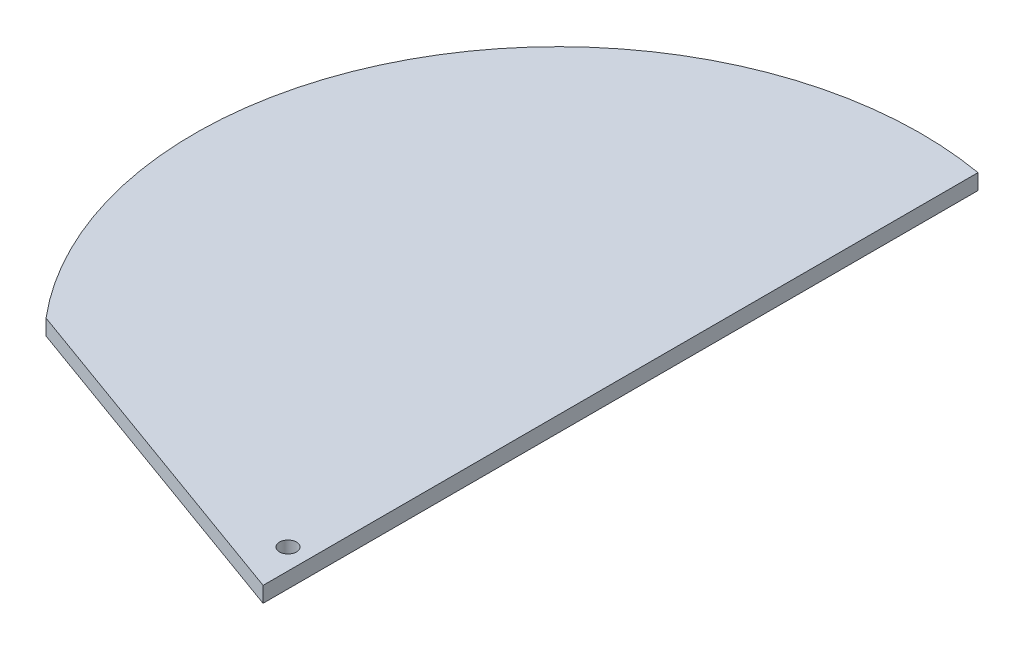
SolidWorks part; units mm, degrees
ref_plane "Front Plane" through (0, 0, 0) normal (0, 0, 1) x (1, 0, 0)
ref_plane "Top Plane" through (0, 0, 0) normal (0, 1, 0) x (1, 0, 0)
ref_plane "Right Plane" through (0, 0, 0) normal (1, 0, 0) x (0, 0, -1)
sketch "Sketch1" plane through (0, 0, 0) normal (0, 1, 0) x (1, 0, 0)
  line L0 (12, 68.9638) -> (12, -68.8024)
  line L1 (12.3, 68.9109) -> (12.3, -68.9109) construction
  line L2 (12, -68.8024) -> (-53.5286, -45.1076)
  line L3 (0, 0) -> (0, 50000) construction
  line L4 (12, -68.8024) -> (12.3, -68.9109) construction
  arc A0 (12, 68.9638) -> (-53.5286, -45.1076) centre (0, 0) ccw
  arc A1 (12, -68.9638) -> (12, 68.9638) centre (0, 0) ccw construction
  circle A2 centre (8, -60) radius 1.65
  dimension "D1" = 140
  dimension "D5" = 3.3
  dimension "D2" = 12
  dimension "D3" = 12.3
  dimension "D4" = 70
  dimension "D6" = 8
  dimension "D7" = 60
extrude "Boss-Extrude1" add sketch "Sketch1" along normal blind 3
